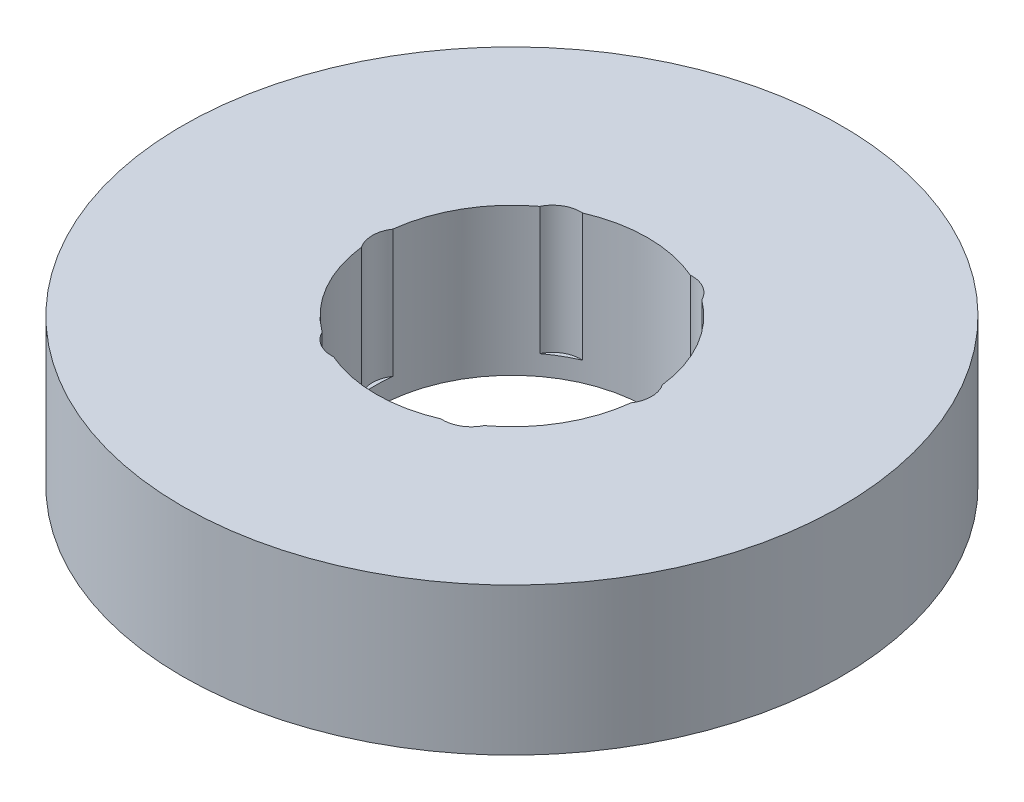
SolidWorks part; units mm, degrees
ref_plane "Front Plane" through (0, 0, 0) normal (0, 0, 1) x (1, 0, 0)
ref_plane "Top Plane" through (0, 0, 0) normal (0, 1, 0) x (1, 0, 0)
ref_plane "Right Plane" through (0, 0, 0) normal (1, 0, 0) x (0, 0, -1)
sketch "Sketch1" plane through (0, 0, 0) normal (0, 1, 0) x (1, 0, 0)
  circle A0 centre (0, 0) radius 42.5
  dimension "FLANGE_OD" = 85
extrude "Boss-Extrude1" add sketch "Sketch1" along normal blind 19
sketch "Sketch2" plane through (0, 0, 0) normal (0, 1, 0) x (1, 0, 0)
  circle A0 centre (0, 0) radius 17.5
  dimension "BORE_D" = 35
extrude "Cut-Extrude1" cut sketch "Sketch2" along normal through all
sketch "Sketch3" plane through (0, 19, 0) normal (0, 1, 0) x (1, 0, 0)
  circle A0 centre (0, 0) radius 14.363 construction
  circle A1 centre (-14.363, 0) radius 3.6334
  dimension "BOLT_D" = 7.2667
  dimension "BOLT_PCD" = 28.7261
extrude "Cut-Extrude2" cut sketch "Sketch3" against normal blind 16.4461
pattern_circular "CirPattern1" count 6 over 360 about axis through (0, 0, 0) along (0, 1, 0) of "Cut-Extrude2"
